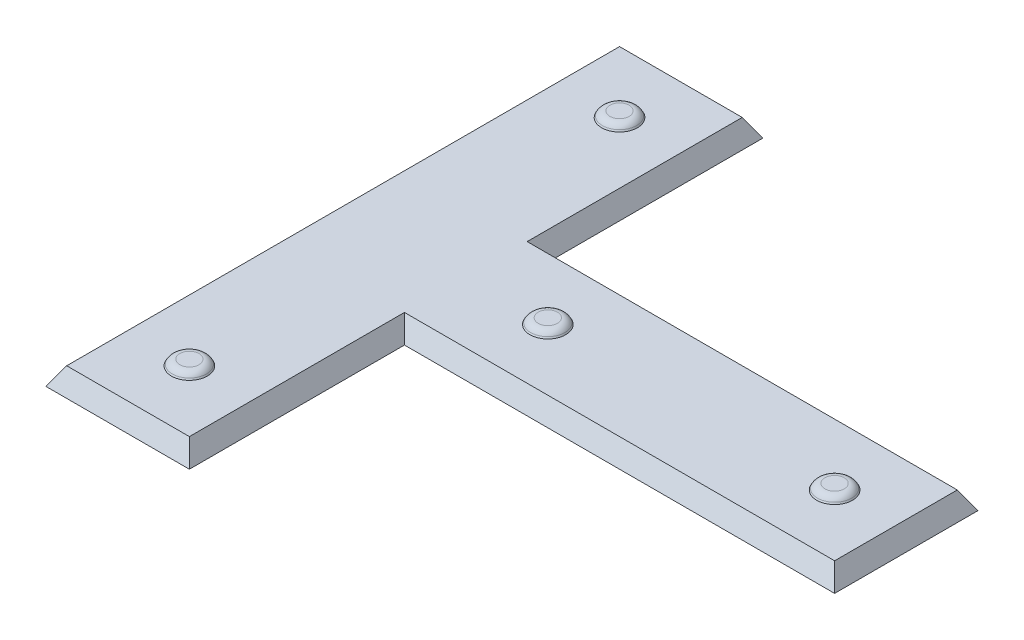
SolidWorks part; units mm, degrees
material "Brass"
ref_plane "Front Plane" through (0, 0, 0) normal (0, 0, 1) x (1, 0, 0)
ref_plane "Top Plane" through (0, 0, 0) normal (0, 1, 0) x (1, 0, 0)
ref_plane "Right Plane" through (0, 0, 0) normal (1, 0, 0) x (0, 0, -1)
ref_axis "X-Axis" through (-171.1325, 0, 0) along (1, 0, 0)
ref_axis "Y-Axis" through (0, 16.7084, 0) along (0, -1, 0)
ref_axis "Z-Axis" through (0, 0, -50.4825) along (0, 0, 1)
sketch "Sketch2" plane through (0, 15.875, 0) normal (0, 1, 0) x (1, 0, 0)
  line L0 (-169.8625, 42.8625) -> (-169.8625, 17.4625)
  line L1 (-169.8625, 17.4625) -> (-163.5125, 17.4625)
  line L2 (-163.5125, 17.4625) -> (-163.5125, 26.9875)
  line L3 (-163.5125, 26.9875) -> (-144.4625, 26.9875)
  line L4 (-144.4625, 26.9875) -> (-144.4625, 33.3375)
  line L5 (-144.4625, 33.3375) -> (-163.5125, 33.3375)
  line L6 (-163.5125, 33.3375) -> (-163.5125, 42.8625)
  line L7 (-163.5125, 42.8625) -> (-169.8625, 42.8625)
  line L9 (-144.4625, 34.925) -> (-144.4625, 33.3375) construction
  line L10 (165.1, 34.925) -> (-165.1, 34.925) construction
  line L11 (-144.4625, 25.4) -> (-144.4625, 26.9875) construction
  line L12 (-165.1, 25.4) -> (165.1, 25.4) construction
  dimension "D1" = 25.4
extrude "Boss-Extrude1" add sketch "Sketch2" along normal blind 0.7937 draft 30
sketch "Sketch3" plane through (0, 16.6687, 0) normal (0, 1, 0) x (1, 0, 0)
  line L0 (-166.6875, 42.4042) -> (-166.6875, 17.9208) construction
  line L1 (-163.9708, 42.4042) -> (-169.4042, 42.4042) construction
  line L2 (-169.4042, 17.9208) -> (-163.9708, 17.9208) construction
  line L3 (-166.6875, 30.1625) -> (-144.9208, 30.1625) construction
  line L4 (-144.9208, 27.4458) -> (-144.9208, 32.8792) construction
  line L5 (-144.4625, 26.9875) -> (-144.4625, 33.3375) construction
  line L6 (-169.8625, 17.4625) -> (-163.5125, 17.4625) construction
  line L7 (-163.5125, 42.8625) -> (-169.8625, 42.8625) construction
  circle A0 centre (-147.6375, 30.1625) radius 0.7938
  circle A1 centre (-160.3375, 30.1625) radius 0.7938
  circle A2 centre (-166.6875, 39.6875) radius 0.7938
  circle A3 centre (-166.6875, 20.6375) radius 0.7938
  dimension "D1" = 1.5875
  dimension "D2" = 3.175
  dimension "D3" = 3.175
  dimension "D4" = 3.175
  dimension "D5" = 12.7
extrude "Boss-Extrude2" add sketch "Sketch3" along normal blind 0.254 draft 30
fillet "Fillet1" radius 0.381 4 edges at (-147.6375, 16.9228, -29.5154) (-160.3375, 16.9228, -29.5154) (-166.6875, 16.9228, -39.0404) (-166.6875, 16.9228, -19.9904)
